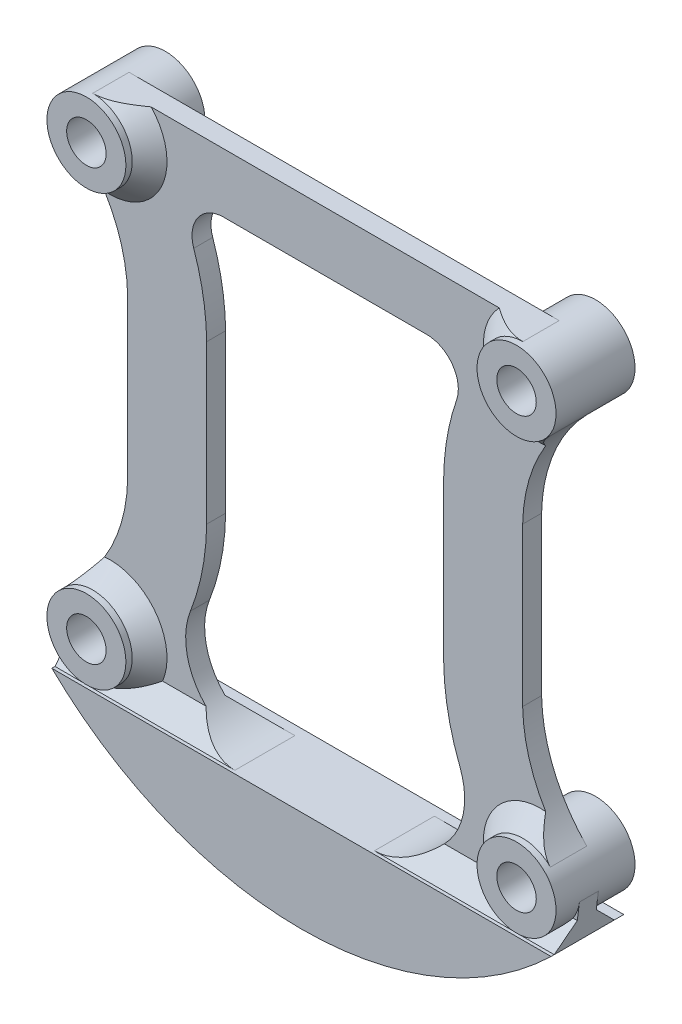
SolidWorks part; units mm, degrees
ref_plane "前视基准面" through (0, 0, 0) normal (0, 0, 1) x (1, 0, 0)
ref_plane "上视基准面" through (0, 0, 0) normal (0, 1, 0) x (1, 0, 0)
ref_plane "右视基准面" through (0, 0, 0) normal (1, 0, 0) x (0, 0, -1)
sketch "草图1" plane through (0, 0, 0) normal (0, 0, 1) x (1, 0, 0)
  line L0 (-38.1213, 0) -> (38.1213, 0) construction
  line L1 (0, -39.2343) -> (0, 39.2343) construction
  line L2 (-15.7987, -16.3) -> (15.7987, -16.3)
  line L3 (0, 0) -> (19.8165, 19.8165) construction
  line L4 (12.5, -5) -> (12.5, 5)
  line L5 (7.5, 5) -> (7.5, -5)
  line L6 (-7.5, 5) -> (-7.5, -5)
  line L7 (-12.5, -5) -> (-12.5, 5)
  line L8 (13.6118, 16.1118) -> (-13.6118, 16.1118)
  line L9 (16.0929, -13.9183) -> (15.7987, -16.3)
  line L10 (6.427, 12.3618) -> (-6.427, 12.3618)
  line L11 (-16.0929, -13.9183) -> (-15.7987, -16.3)
  line L12 (-3, -19.25) -> (3, -19.25)
  line L14 (3.866, -20.75) -> (2.8434, -22.5212)
  line L16 (-3.866, -20.75) -> (-2.8434, -22.5212)
  circle A2 centre (0, 0) radius 19.25 construction
  circle A5 centre (13.6118, 13.6118) radius 1.25
  circle A6 centre (13.6118, 13.6118) radius 2.5
  circle A7 centre (13.6118, -13.6118) radius 1.25
  circle A8 centre (13.6118, -13.6118) radius 2.5
  circle A9 centre (-13.6118, -13.6118) radius 1.25
  circle A10 centre (-13.6118, -13.6118) radius 2.5
  circle A11 centre (-13.6118, 13.6118) radius 1.25
  circle A12 centre (-13.6118, 13.6118) radius 2.5
  arc A13 (15.3565, 11.8213) -> (12.5, 5) centre (22.4984, 4.8218) ccw
  arc A17 (7.5, -5) -> (8.5269, -10.279) centre (22.4984, -4.8218) ccw
  arc A18 (7.5, 5) -> (8.3178, 9.71) centre (22.4984, 4.8218) cw
  arc A19 (15.3565, -11.8213) -> (12.5, -5) centre (22.4984, -4.8218) cw
  arc A20 (-15.3565, -11.8213) -> (-12.5, -5) centre (-22.4984, -4.8218) ccw
  arc A21 (-7.5, -5) -> (-8.5269, -10.279) centre (-22.4984, -4.8218) cw
  arc A22 (-15.3565, 11.8213) -> (-12.5, 5) centre (-22.4984, 4.8218) cw
  arc A23 (-7.5, 5) -> (-8.3178, 9.71) centre (-22.4984, 4.8218) ccw
  arc A24 (8.3178, 9.71) -> (6.427, 12.3618) centre (6.427, 10.3618) ccw
  arc A25 (-8.3178, 9.71) -> (-6.427, 12.3618) centre (-6.427, 10.3618) cw
  arc A26 (11.73, 15.2633) -> (11.8344, 15.3699) centre (22.4984, 4.8218) cw
  arc A27 (-11.73, 15.2633) -> (-11.8344, 15.3699) centre (-22.4984, 4.8218) ccw
  arc A28 (4.4147, -16.3) -> (8.5269, -10.279) centre (4.4147, -11.8853) ccw
  arc A29 (-4.4147, -16.3) -> (-8.5269, -10.279) centre (-4.4147, -11.8853) cw
  arc A30 (11.73, -15.2633) -> (11.8344, -15.3699) centre (22.4984, -4.8218) ccw
  arc A31 (-11.73, -15.2633) -> (-11.8344, -15.3699) centre (-22.4984, -4.8218) cw
  arc A32 (3.866, -20.75) -> (3, -19.25) centre (3, -20.25) ccw
  arc A33 (-3.866, -20.75) -> (-3, -19.25) centre (-3, -20.25) cw
  arc A34 (-15.7987, -16.3) -> (15.7987, -16.3) centre (0, 0) ccw
  point P23 (0, 0)
  point P27 (0, 0)
  point P56 (0, 0)
  point P64 (0, -19.25)
  dimension "D1" = 2.5
  dimension "D2" = 5
  dimension "D3" = 22.7
  dimension "D6" = 38.5
  dimension "D8" = 7.5
  dimension "D12" = 10
  dimension "D13" = 12.3618
  dimension "D5" = 12.5
  dimension "D11" = 2
  dimension "D16" = 3
  dimension "D15" = 1
  dimension "D4" = 4
  dimension "D7" = 45
  dimension "D9" = 16.3
  dimension "D10" = 5
  dimension "D14" = 60
extrude "凸台-拉伸1" add sketch "草图1" along normal blind 5 contours A12 A11 | A6 A5 | A10 A9 | A8 A7 region at (-15.9039, -12.8069, 0) region at (14.3956, -15.9112, 0) region at (-15.8621, 14.5269, 0) region at (15.3296, 15.3296, 0)
extrude "凸台-拉伸2" add sketch "草图1<5>" along normal blind 3.5 contours L2 A29 A21 L6 A23 A25 L10 A24 A18 L5 A17 A28 L9 A8 A19 L4 A13 A6 L8 A12 A22 L7 A20 A10 L11 region at (-15.9005, -15.1036, 0)
sketch "草图1<5>" plane through (0, 0, 0) normal (0, 0, 1) x (1, 0, 0) same geometry as "草图1"
extrude "切除-拉伸1" cut sketch "草图1<6>" along normal blind 2.3 contours L2 A29 A21 L6 A23 A25 L10 A24 A18 L5 A17 A28 L9 A8 A19 L4 A13 A6 L8 A12 A22 L7 A20 A10 L11 region at (-15.9005, -15.1036, 0)
sketch "草图1<6>" plane through (0, 0, 0) normal (0, 0, 1) x (1, 0, 0) same geometry as "草图1"
extrude "凸台-拉伸3" add sketch "草图1<7>" along normal blind 2 contours L16 A34 L14 A32 L12 A33 region at (0, -20.8659, 0)
sketch "草图1<7>" plane through (0, 0, 0) normal (0, 0, 1) x (1, 0, 0) same geometry as "草图1"
extrude "凸台-拉伸5" add sketch "草图1<12>" along normal blind 5 contours L2 A34 L16 A33 L12 A32 L14 | L16 A34 L14 A32 L12 A33 region at (0, -18.4807, 0) region at (0, -20.8659, 0)
sketch "草图1<12>" plane through (0, 0, 0) normal (0, 0, 1) x (1, 0, 0) same geometry as "草图1"
extrude "切除-拉伸2" cut sketch "草图1<9>" along normal blind 3 contours L16 A34 L14 A32 L12 A33 region at (0, -20.8659, 0)
sketch "草图1<9>" plane through (0, 0, 0) normal (0, 0, 1) x (1, 0, 0) same geometry as "草图1"
extrude "切除-拉伸4" cut sketch "草图1<10>" along normal blind 0.4 contours L2 A34 L16 A33 L12 A32 L14 region at (0, -18.4807, 0)
sketch "草图1<10>" plane through (0, 0, 0) normal (0, 0, 1) x (1, 0, 0) same geometry as "草图1"
chamfer "倒角1" distance 1.3 angle 45 4 edges at (10.1067, -16.3, 2.3) (-10.1067, -16.3, 2.3) (10.1067, -16.3, 3.5) (-10.1067, -16.3, 3.5)
chamfer "倒角3" distance 1.1 angle 45 4 edges at (12.0137, -11.6893, 3.5) (11.296, 12.6701, 3.5) (-11.296, 12.6701, 3.5) (-12.0137, -11.6893, 3.5)
